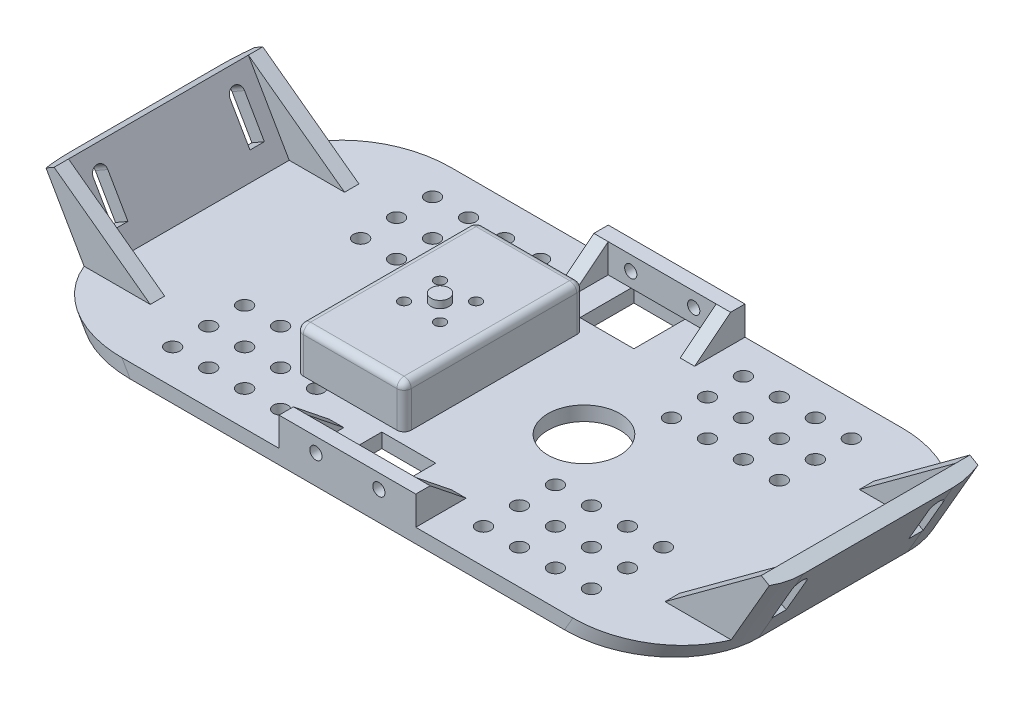
SolidWorks part; units mm, degrees
note: The reader was unsure of these and kept them because the rebuilt part matched: shared geometry of "草图21<3>", "草图22<3>".
ref_plane "前视基准面" through (0, 0, 0) normal (0, 0, 1) x (1, 0, 0)
ref_plane "上视基准面" through (0, 0, 0) normal (0, 1, 0) x (1, 0, 0)
ref_plane "右视基准面" through (0, 0, 0) normal (1, 0, 0) x (0, 0, -1)
sketch "草图1" plane through (0, 0, 0) normal (0, 0, 1) x (1, 0, 0)
  line L0 (0, 38.1234) -> (0, -105.8805) construction
  line L1 (-100, -37.7728) -> (100, -37.7728)
  line L2 (-100, -37.7728) -> (-100, -33.7728)
  line L3 (-100, -33.7728) -> (100, -33.7728)
  line L4 (100, -37.7728) -> (100, -33.7728)
  circle A1 centre (-8.75, -29.7728) radius 1.7 construction
  dimension "D1" = 4
  dimension "D2" = 4
  dimension "D3" = 200
extrude "凸台-拉伸1" add sketch "草图1" against normal blind 45.75
sketch "草图2" plane through (0, 0, -45.75) normal (0, 0, -1) x (-1, 0, 0)
  line L0 (0, 0) -> (0, -33.7728) construction
  line L1 (-100, -33.7728) -> (100, -33.7728) construction
  line L3 (-15, -25.7728) -> (15, -25.7728)
  line L4 (-15, -25.7728) -> (-15, -33.7728)
  line L5 (-15, -33.7728) -> (15, -33.7728)
  line L6 (15, -25.7728) -> (15, -33.7728)
  circle A0 centre (-8.75, -29.7728) radius 1.7
  circle A1 centre (8.75, -29.7728) radius 1.7
  dimension "D1" = 30
  dimension "D2" = 8
extrude "凸台-拉伸2" add sketch "草图2" against normal blind 4
sketch "草图3" plane through (-15, 0, 0) normal (-1, 0, 0) x (0, 0, 1)
  line L0 (-41.75, -25.7728) -> (-31.75, -33.7728)
  line L1 (-45.75, -33.7728) -> (0, -33.7728) construction
  line L2 (-31.75, -33.7728) -> (-41.75, -33.7728)
  line L4 (-45.75, -25.7728) -> (-45.75, -33.7728)
  line L5 (-45.75, -33.7728) -> (-41.75, -33.7728)
  line L6 (-41.75, -33.7728) -> (-41.75, -25.7728)
  line L7 (-41.75, -25.7728) -> (-45.75, -25.7728)
  line L8 (-45.75, -25.7728) -> (-45.75, -33.7728)
  line L9 (-45.75, -33.7728) -> (-41.75, -33.7728)
  line L11 (-41.75, -25.7728) -> (-45.75, -25.7728)
  dimension "D2" = 10
  dimension "D1" = 0
extrude "凸台-拉伸3" add sketch "草图3" along normal blind 4
sketch "草图4" plane through (15, 0, 0) normal (1, 0, 0) x (0, 0, -1)
  line L5 (41.75, -25.7728) -> (31.75, -33.7728)
  line L6 (31.75, -33.7728) -> (41.75, -33.7728)
  line L7 (41.75, -33.7728) -> (45.75, -33.7728)
  line L8 (45.75, -33.7728) -> (45.75, -25.7728)
  line L9 (45.75, -25.7728) -> (41.75, -25.7728)
  line L10 (41.75, -25.7728) -> (31.75, -33.7728)
  line L11 (31.75, -33.7728) -> (41.75, -33.7728)
  line L12 (41.75, -33.7728) -> (45.75, -33.7728)
  line L13 (45.75, -33.7728) -> (45.75, -25.7728)
  line L14 (45.75, -25.7728) -> (41.75, -25.7728)
  dimension "D1" = 0
extrude "凸台-拉伸4" add sketch "草图4" along normal blind 4
sketch "草图5" plane through (0, 0, -45.75) normal (0, 0, -1) x (-1, 0, 0)
  line L0 (97.0733, -24.1862) -> (87.6203, -40.5592)
  line L3 (87.6203, -40.5592) -> (102.5438, -40.5696)
  line L4 (102.5438, -40.5696) -> (102.5438, -24.1862)
  line L5 (102.5438, -24.1862) -> (97.0733, -24.1862)
  line L6 (0, 27.5212) -> (0, 0) construction
  line L7 (-102.5438, -24.1862) -> (-97.0733, -24.1862)
  line L8 (-102.5438, -40.5696) -> (-102.5438, -24.1862)
  line L9 (-87.6203, -40.5592) -> (-102.5438, -40.5696)
  line L10 (-97.0733, -24.1862) -> (-87.6203, -40.5592)
extrude "切除-拉伸1" cut sketch "草图5" against normal blind 64.8
mirror "镜向1" about plane through (0, 0, 0) normal (0, 0, -1) of bodies 105
sketch "草图6" plane through (-83.2779, -48.0805, 0) normal (-0.866, -0.5, 0) x (0, 0, 1)
  line L0 (0, 0) -> (0, 32.6716) construction
  line L1 (-45.75, 11.9023) -> (45.75, 11.9023) construction
  line L2 (-25, 11.9023) -> (25, 11.9023)
  line L3 (-25, 11.9023) -> (-25, 36.9023)
  line L4 (-25, 36.9023) -> (25, 36.9023)
  line L5 (25, 11.9023) -> (25, 36.9023)
  line L6 (19, 31.0422) -> (-23.578, 31.0422) construction
  line L8 (-21, 31.0422) -> (-21, 20.0192)
  line L9 (-21, 20.0192) -> (-17, 20.0192)
  line L10 (-17, 31.0422) -> (-17, 20.0192)
  line L12 (17, 31.0422) -> (17, 19.8442)
  line L13 (17, 19.8442) -> (21, 19.8442)
  line L14 (21, 31.0422) -> (21, 19.8442)
  arc A0 (-17, 31.0422) -> (-21, 31.0422) centre (-19, 31.0422) ccw
  arc A1 (21, 31.0422) -> (17, 31.0422) centre (19, 31.0422) ccw
  dimension "D1" = 50
  dimension "D2" = 25
extrude "凸台-拉伸5" add sketch "草图6" against normal blind 4
sketch "草图7" plane through (0, 0, 25) normal (0, 0, 1) x (1, 0, 0)
  line L0 (-91.5384, -33.7728) -> (-101.729, -16.1222)
  line L2 (-101.729, -16.1222) -> (-98.2649, -14.1222)
  line L3 (-98.2649, -14.1222) -> (-101.729, -16.1222) construction
  line L4 (-86.9196, -33.7728) -> (-98.2649, -14.1222) construction
  line L5 (-98.2649, -14.1222) -> (-71.5384, -33.7728)
  line L6 (-19, -33.7728) -> (-91.5384, -33.7728) construction
  line L7 (-71.5384, -33.7728) -> (-91.5384, -33.7728)
  dimension "D1" = 20
extrude "凸台-拉伸6" add sketch "草图7" along normal blind 4
sketch "草图8" plane through (0, 0, -25) normal (0, 0, -1) x (-1, 0, 0)
  line L4 (91.5384, -33.7728) -> (101.729, -16.1222)
  line L5 (101.729, -16.1222) -> (98.2649, -14.1222)
  line L6 (98.2649, -14.1222) -> (71.5384, -33.7728)
  line L7 (71.5384, -33.7728) -> (91.5384, -33.7728)
  line L8 (91.5384, -33.7728) -> (101.729, -16.1222)
  line L9 (101.729, -16.1222) -> (98.2649, -14.1222)
  line L10 (98.2649, -14.1222) -> (71.5384, -33.7728)
  line L11 (71.5384, -33.7728) -> (91.5384, -33.7728)
  dimension "D1" = 0
extrude "凸台-拉伸7" add sketch "草图8" along normal blind 4
mirror "镜向2" about plane through (0, 0, 0) normal (1, 0, 0) of "凸台-拉伸7", "凸台-拉伸6", "凸台-拉伸5"
fillet "圆角1" radius 25 18 edges at (90.3837, -35.7728, 45.75) (-90.3837, -35.7728, 45.75) (-96.0432, -25.9703, -21) (-95.9995, -26.046, 21) (-96.6337, -24.9475, 29) (-91.5384, -33.7728, -37.375) (-96.6337, -24.9475, -29) (96.0432, -25.9703, -21) (95.9995, -26.046, 21) (91.5384, -33.7728, 37.375) (96.6337, -24.9475, 29) (96.6337, -24.9475, -29) (-91.5384, -33.7728, 37.375) (-90.3837, -35.7728, -45.75) (91.5384, -33.7728, -37.375) (90.3837, -35.7728, -45.75)
sketch "草图12" plane through (0, -33.7728, 0) normal (0, 1, 0) x (1, 0, 0)
  line L0 (33.5526, 0) -> (-51.6593, 0) construction
  line L1 (-8.6552, -42.532) -> (-8.6552, -27.532)
  line L2 (6.3448, 42.532) -> (-8.6552, 42.532)
  line L3 (6.3448, 42.532) -> (6.3448, 27.532)
  line L4 (6.3448, 27.532) -> (-8.6552, 27.532)
  line L5 (-8.6552, 42.532) -> (-8.6552, 27.532)
  line L6 (6.3448, -27.532) -> (-8.6552, -27.532)
  line L7 (6.3448, -42.532) -> (6.3448, -27.532)
  line L8 (6.3448, -42.532) -> (-8.6552, -42.532)
  circle A0 centre (58.1968, 36.1191) radius 2
  circle A1 centre (48.1968, 36.1191) radius 2
  circle A2 centre (38.1968, 36.1191) radius 2
  circle A3 centre (28.1968, 36.1191) radius 2
  circle A4 centre (48.1968, 26.1191) radius 2
  circle A5 centre (38.1968, 26.1191) radius 2
  circle A6 centre (28.1968, 26.1191) radius 2
  circle A7 centre (48.1968, 16.1191) radius 2
  circle A8 centre (38.1968, 16.1191) radius 2
  circle A9 centre (28.1968, 16.1191) radius 2
  circle A10 centre (58.1968, 26.1191) radius 2
  circle A11 centre (58.1968, 16.1191) radius 2
  circle A12 centre (-58.1968, 16.1191) radius 2
  circle A13 centre (-58.1968, 26.1191) radius 2
  circle A14 centre (-28.1968, 16.1191) radius 2
  circle A15 centre (-38.1968, 16.1191) radius 2
  circle A16 centre (-48.1968, 16.1191) radius 2
  circle A17 centre (-28.1968, 26.1191) radius 2
  circle A18 centre (-38.1968, 26.1191) radius 2
  circle A19 centre (-48.1968, 26.1191) radius 2
  circle A20 centre (-28.1968, 36.1191) radius 2
  circle A21 centre (-38.1968, 36.1191) radius 2
  circle A22 centre (-48.1968, 36.1191) radius 2
  circle A23 centre (-58.1968, 36.1191) radius 2
  circle A24 centre (-58.1968, -36.1191) radius 2
  circle A25 centre (-48.1968, -36.1191) radius 2
  circle A26 centre (-38.1968, -36.1191) radius 2
  circle A27 centre (-28.1968, -36.1191) radius 2
  circle A28 centre (-48.1968, -26.1191) radius 2
  circle A29 centre (-38.1968, -26.1191) radius 2
  circle A30 centre (-28.1968, -26.1191) radius 2
  circle A31 centre (-48.1968, -16.1191) radius 2
  circle A32 centre (-38.1968, -16.1191) radius 2
  circle A33 centre (-28.1968, -16.1191) radius 2
  circle A34 centre (-58.1968, -26.1191) radius 2
  circle A35 centre (-58.1968, -16.1191) radius 2
  circle A36 centre (58.1968, -16.1191) radius 2
  circle A37 centre (58.1968, -26.1191) radius 2
  circle A38 centre (28.1968, -16.1191) radius 2
  circle A39 centre (38.1968, -16.1191) radius 2
  circle A40 centre (48.1968, -16.1191) radius 2
  circle A41 centre (28.1968, -26.1191) radius 2
  circle A42 centre (38.1968, -26.1191) radius 2
  circle A43 centre (48.1968, -26.1191) radius 2
  circle A44 centre (28.1968, -36.1191) radius 2
  circle A45 centre (38.1968, -36.1191) radius 2
  circle A46 centre (48.1968, -36.1191) radius 2
  circle A47 centre (58.1968, -36.1191) radius 2
  dimension "D1" = 4
  dimension "D3" = 4
  dimension "D2" = 3
extrude "切除-拉伸5" cut sketch "草图12" against normal blind 13
sketch "草图14" plane through (0, -33.7728, 0) normal (0, 1, 0) x (1, 0, 0)
  line L0 (-10.9, -20.6) -> (10.75, -20.6)
  line L1 (-13.9, -23.6) -> (13.75, -23.6)
  line L2 (13.75, -23.6) -> (13.75, 26.2)
  line L3 (-13.9, 26.2) -> (13.75, 26.2)
  line L4 (-13.9, -23.6) -> (-13.9, 26.2)
  line L5 (10.75, -20.6) -> (10.75, 23.2)
  line L6 (-10.9, 23.2) -> (10.75, 23.2)
  line L7 (-10.9, -20.6) -> (-10.9, 23.2)
  dimension "D1" = 3
extrude "凸台-拉伸8" [suppressed] add sketch "草图14" along normal blind 10
sketch "草图15" plane through (0, -33.7728, 0) normal (0, 1, 0) x (1, 0, 0)
  line L4 (-8.6552, -41.75) -> (-8.6552, -27.532)
  line L5 (-8.6552, -41.75) -> (-8.6552, -27.532)
  line L6 (-8.6552, -27.532) -> (6.3448, -27.532)
  line L7 (-8.6552, -27.532) -> (6.3448, -27.532)
  line L8 (6.3448, -27.532) -> (6.3448, -41.75)
  line L9 (6.3448, -27.532) -> (6.3448, -41.75)
  line L10 (6.3448, -41.75) -> (15, -41.75)
  line L11 (6.3448, -41.75) -> (15, -41.75)
  line L48 (15, -41.75) -> (15, -31.75)
  line L49 (15, -41.75) -> (15, -31.75)
  line L50 (15, -31.75) -> (19, -31.75)
  line L51 (15, -31.75) -> (19, -31.75)
  line L52 (19, -31.75) -> (19, -45.75)
  line L53 (19, -31.75) -> (19, -45.75)
  line L54 (19, -45.75) -> (62.6709, -45.75)
  line L55 (19, -45.75) -> (62.6709, -45.75)
  line L56 (89.9213, -29) -> (71.5384, -29)
  line L57 (89.9213, -29) -> (71.5384, -29)
  line L58 (71.5384, -29) -> (71.5384, -25)
  line L59 (71.5384, -29) -> (71.5384, -25)
  line L60 (71.5384, -25) -> (86.9196, -25)
  line L61 (71.5384, -25) -> (86.9196, -25)
  line L62 (86.9196, -25) -> (86.9196, 25)
  line L63 (86.9196, -25) -> (86.9196, 25)
  line L64 (86.9196, 25) -> (71.5384, 25)
  line L65 (86.9196, 25) -> (71.5384, 25)
  line L66 (71.5384, 25) -> (71.5384, 29)
  line L67 (71.5384, 25) -> (71.5384, 29)
  line L68 (71.5384, 29) -> (89.9213, 29)
  line L69 (71.5384, 29) -> (89.9213, 29)
  line L70 (62.6709, 45.75) -> (19, 45.75)
  line L71 (62.6709, 45.75) -> (19, 45.75)
  line L72 (19, 45.75) -> (19, 31.75)
  line L73 (19, 45.75) -> (19, 31.75)
  line L74 (19, 31.75) -> (15, 31.75)
  line L75 (19, 31.75) -> (15, 31.75)
  line L76 (15, 31.75) -> (15, 41.75)
  line L77 (15, 31.75) -> (15, 41.75)
  line L78 (15, 41.75) -> (6.3448, 41.75)
  line L79 (15, 41.75) -> (6.3448, 41.75)
  line L80 (6.3448, 41.75) -> (6.3448, 27.532)
  line L81 (6.3448, 41.75) -> (6.3448, 27.532)
  line L82 (6.3448, 27.532) -> (-8.6552, 27.532)
  line L83 (6.3448, 27.532) -> (-8.6552, 27.532)
  line L84 (-8.6552, 27.532) -> (-8.6552, 41.75)
  line L85 (-8.6552, 27.532) -> (-8.6552, 41.75)
  line L86 (-8.6552, 41.75) -> (-15, 41.75)
  line L87 (-8.6552, 41.75) -> (-15, 41.75)
  line L88 (-15, 41.75) -> (-15, 31.75)
  line L89 (-15, 41.75) -> (-15, 31.75)
  line L90 (-15, 31.75) -> (-19, 31.75)
  line L91 (-15, 31.75) -> (-19, 31.75)
  line L92 (-19, 31.75) -> (-19, 45.75)
  line L93 (-19, 31.75) -> (-19, 45.75)
  line L94 (-19, 45.75) -> (-62.6709, 45.75)
  line L95 (-19, 45.75) -> (-62.6709, 45.75)
  line L96 (-89.9213, 29) -> (-71.5384, 29)
  line L97 (-89.9213, 29) -> (-71.5384, 29)
  line L98 (-71.5384, 29) -> (-71.5384, 25)
  line L99 (-71.5384, 29) -> (-71.5384, 25)
  line L100 (-71.5384, 25) -> (-86.9196, 25)
  line L101 (-71.5384, 25) -> (-86.9196, 25)
  line L102 (-86.9196, 25) -> (-86.9196, -25)
  line L103 (-86.9196, 25) -> (-86.9196, -25)
  line L104 (-86.9196, -25) -> (-71.5384, -25)
  line L105 (-86.9196, -25) -> (-71.5384, -25)
  line L106 (-71.5384, -25) -> (-71.5384, -29)
  line L107 (-71.5384, -25) -> (-71.5384, -29)
  line L108 (-71.5384, -29) -> (-89.9213, -29)
  line L109 (-71.5384, -29) -> (-89.9213, -29)
  line L110 (-62.6709, -45.75) -> (-19, -45.75)
  line L111 (-62.6709, -45.75) -> (-19, -45.75)
  line L112 (-19, -45.75) -> (-19, -31.75)
  line L113 (-19, -45.75) -> (-19, -31.75)
  line L114 (-19, -31.75) -> (-15, -31.75)
  line L115 (-19, -31.75) -> (-15, -31.75)
  line L116 (-15, -31.75) -> (-15, -41.75)
  line L117 (-15, -31.75) -> (-15, -41.75)
  line L118 (-15, -41.75) -> (-8.6552, -41.75)
  line L119 (-15, -41.75) -> (-8.6552, -41.75)
  ellipse E4 centre (62.6709, -20.75) end of major axis (33.8034, -20.75) minor radius 25 (62.6709, -45.75) -> (89.9213, -29) ccw
  ellipse E5 centre (62.6709, -20.75) end of major axis (33.8034, -20.75) minor radius 25 (62.6709, -45.75) -> (89.9213, -29) ccw
  ellipse E6 centre (62.6709, 20.75) end of major axis (33.8034, 20.75) minor radius 25 (89.9213, 29) -> (62.6709, 45.75) ccw
  ellipse E7 centre (62.6709, 20.75) end of major axis (33.8034, 20.75) minor radius 25 (89.9213, 29) -> (62.6709, 45.75) ccw
  ellipse E8 centre (-62.6709, 20.75) end of major axis (-91.5384, 20.75) minor radius 25 (-62.6709, 45.75) -> (-89.9213, 29) ccw
  ellipse E9 centre (-62.6709, 20.75) end of major axis (-91.5384, 20.75) minor radius 25 (-62.6709, 45.75) -> (-89.9213, 29) ccw
  ellipse E10 centre (-62.6709, -20.75) end of major axis (-91.5384, -20.75) minor radius 25 (-89.9213, -29) -> (-62.6709, -45.75) ccw
  ellipse E11 centre (-62.6709, -20.75) end of major axis (-91.5384, -20.75) minor radius 25 (-89.9213, -29) -> (-62.6709, -45.75) ccw
  dimension "D1" = 0
extrude "凸台-拉伸9" [suppressed] add sketch "草图15" along normal blind 2.35
sketch "草图18" [suppressed] plane through (-13.9, 0, 0) normal (-1, 0, 0) x (0, 0, 1)
  line L0 (0, 20.1614) -> (0, 0) construction
  line L1 (-18, 15.3115) -> (-9, 15.3115)
  line L2 (-18, 15.3115) -> (-18, -25.0647)
  line L3 (-18, -25.0647) -> (-9, -25.0647)
  line L4 (-9, 15.3115) -> (-9, -25.0647)
  line L5 (9, 15.3115) -> (9, -25.0647)
  line L6 (18, -25.0647) -> (9, -25.0647)
  line L7 (18, 15.3115) -> (18, -25.0647)
  line L8 (18, 15.3115) -> (9, 15.3115)
  dimension "D1" = 9
  dimension "D2" = 9
extrude "凸台-拉伸10" [suppressed] add sketch "草图18" against normal blind 3
sketch "草图19" [suppressed] plane through (13.75, 0, 0) normal (1, 0, 0) x (0, 0, -1)
  line L4 (-9, -25.0647) -> (-9, 15.3115)
  line L5 (-18, -25.0647) -> (-9, -25.0647)
  line L6 (-18, 15.3115) -> (-18, -25.0647)
  line L7 (-9, 15.3115) -> (-18, 15.3115)
  line L8 (-9, -25.0647) -> (-9, 15.3115)
  line L9 (-18, -25.0647) -> (-9, -25.0647)
  line L10 (-18, 15.3115) -> (-18, -25.0647)
  line L11 (-9, 15.3115) -> (-18, 15.3115)
  line L12 (18, 15.3115) -> (9, 15.3115)
  line L13 (9, 15.3115) -> (9, -25.0647)
  line L14 (9, -25.0647) -> (18, -25.0647)
  line L15 (18, -25.0647) -> (18, 15.3115)
  line L16 (18, 15.3115) -> (9, 15.3115)
  line L17 (9, 15.3115) -> (9, -25.0647)
  line L18 (9, -25.0647) -> (18, -25.0647)
  line L19 (18, -25.0647) -> (18, 15.3115)
  dimension "D1" = 0
  dimension "D2" = 0
extrude "凸台-拉伸11" [suppressed] add sketch "草图19" against normal blind 3
sketch "草图20" [suppressed] plane through (-13.9, 0, 0) normal (-1, 0, 0) x (0, 0, 1)
  line L0 (0, 21.6193) -> (0, 0) construction
  circle A0 centre (-13.5, 12.4612) radius 1.75
  circle A1 centre (13.5, 12.4612) radius 1.75
extrude "切除-拉伸6" [suppressed] cut sketch "草图20" against normal blind 38
fillet "圆角2" [suppressed] radius 5
fillet "圆角3" [suppressed] radius 3
sketch "草图22" plane through (0, -33.7728, 0) normal (0, 1, 0) x (1, 0, 0)
  line L0 (-61.6819, 0) -> (21.3982, 0) construction
  line L1 (-30, 20) -> (-30, -20)
  line L2 (-30, -20) -> (-10, -20)
  line L3 (-35, 25) -> (-5, 25)
  line L4 (-35, 25) -> (-35, -25)
  line L5 (-35, -25) -> (-5, -25)
  line L6 (-5, 25) -> (-5, -25)
  line L7 (-35, 25) -> (-5, -25) construction
  line L8 (-35, -25) -> (-5, 25) construction
  line L9 (-10, 20) -> (-10, -20)
  line L10 (-30, 20) -> (-10, 20)
  point P5 (-20, 0)
  dimension "D1" = 50
  dimension "D2" = 30
  dimension "D3" = 20
  dimension "D4" = 5
extrude "凸台-拉伸13" add sketch "草图22" along normal blind 12 contours L4 L5 L6 L3
sketch "草图21" plane through (0, -21.7728, 0) normal (0, 1, 0) x (1, 0, 0)
  line L0 (-44.3808, 0) -> (48.024, 0) construction
  line L1 (-20, 60.444) -> (-20, -63.0936) construction
  circle A0 centre (-20, 0) radius 2.5
  circle A1 centre (-25, 5) radius 1.5
  circle A2 centre (-15, 5) radius 1.5
  circle A3 centre (-15, -5) radius 1.5
  circle A4 centre (-25, -5) radius 1.5
  circle A5 centre (20, 0) radius 10
  point P5 (-20, 0)
  point P19 (-20, 0)
  dimension "D2" = 5
  dimension "D3" = 3
  dimension "D7" = 40
  dimension "D8" = 20
  dimension "D1" = 20
  dimension "D4" = 5
  dimension "D5" = 5
  dimension "D6" = 4
extrude "切除-拉伸7" cut sketch "草图21" against normal through all and the other way through all contours A1 | A2 | A4 | A3 | A5 | A0
extrude "凸台-拉伸12" add sketch "草图21<3>" along normal blind 2 contours A0
sketch "草图21<3>" plane through (0, -21.7728, 0) normal (0, 1, 0) x (1, 0, 0) same geometry as "草图21"
extrude "切除-拉伸8" cut sketch "草图22<3>" along normal offset from surface 5 and the other way through all contours L2 L9 L10 L1 up to face at (-17.5, -21.7728, 0)
sketch "草图22<3>" plane through (0, -33.7728, 0) normal (0, 1, 0) x (1, 0, 0) same geometry as "草图22"
fillet "圆角4" radius 2 8 edges at (-35, -27.7728, -25) (-5, -27.7728, -25) (-5, -27.7728, 25) (-35, -27.7728, 25) (-20, -21.7728, -25) (-5, -21.7728, 0) (-20, -21.7728, 25) (-35, -21.7728, 0)
